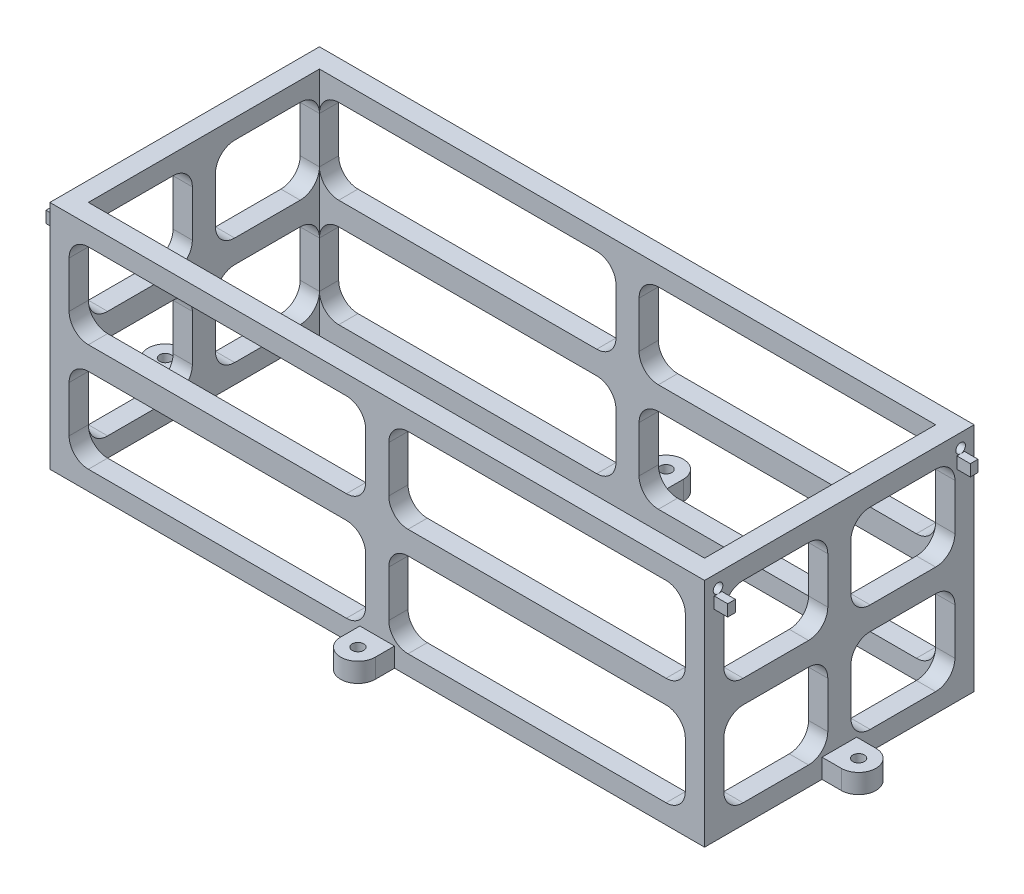
SolidWorks part; units mm, degrees
ref_plane "Front Plane" through (0, 0, 0) normal (0, 0, 1) x (1, 0, 0)
ref_plane "Top Plane" through (0, 0, 0) normal (0, 1, 0) x (1, 0, 0)
ref_plane "Right Plane" through (0, 0, 0) normal (1, 0, 0) x (0, 0, -1)
sketch "Sketch1" plane through (0, 0, 0) normal (0, 1, 0) x (1, 0, 0)
  line L1 (-85, -35) -> (85, -35)
  line L2 (-85, -35) -> (-85, 35)
  line L3 (-85, 35) -> (85, 35)
  line L4 (85, -35) -> (85, 35)
  line L5 (-85, -35) -> (85, 35) construction
  line L6 (-85, 35) -> (85, -35) construction
  point P0 (0, 0)
  dimension "D1" = 70
  dimension "D2" = 170
extrude "Boss-Extrude1" add sketch "Sketch1" along normal blind 60
shell "Shell1" thickness 5 removed face at (0, 60, 0) removed face at (0, 0, 0)
sketch "Sketch3" plane through (-85, 0, 0) normal (-1, 0, 0) x (0, 0, 1)
  line L0 (-35, 30) -> (35, 30) construction
  line L1 (-35, 60) -> (-35, 0) construction
  line L2 (35, 60) -> (35, 0) construction
  line L3 (-35, 60) -> (35, 60) construction
  line L4 (-30, 5) -> (30, 5)
  line L5 (-30, 5) -> (-30, 55)
  line L6 (-30, 55) -> (30, 55)
  line L7 (30, 5) -> (30, 55)
  line L8 (-30, 5) -> (30, 55) construction
  line L9 (-30, 55) -> (30, 5) construction
  point P6 (0, 30)
  dimension "D1" = 5
  dimension "D2" = 5
sketch "Sketch4" plane through (85, 0, 0) normal (1, 0, 0) x (0, 0, -1)
  line L0 (0, 60) -> (0, 0) construction
  line L1 (-35, 60) -> (35, 60) construction
  line L2 (-35, 30) -> (35, 30) construction
  line L3 (-35, 60) -> (-35, 0) construction
  line L4 (35, 60) -> (35, 0) construction
  line L5 (-35, 0) -> (35, 0) construction
  line L6 (-25, 55) -> (-8, 55)
  line L7 (-30, 50) -> (-30, 38)
  line L8 (-25, 33) -> (-8, 33)
  line L9 (-3, 50) -> (-3, 38)
  line L10 (-25, 27) -> (-8, 27)
  line L11 (-30, 22) -> (-30, 10)
  line L12 (-25, 5) -> (-8, 5)
  line L13 (-3, 22) -> (-3, 10)
  line L14 (8, 55) -> (25, 55)
  line L15 (3, 50) -> (3, 38)
  line L16 (8, 33) -> (25, 33)
  line L17 (30, 50) -> (30, 38)
  line L18 (8, 27) -> (25, 27)
  line L19 (3, 22) -> (3, 10)
  line L20 (8, 5) -> (25, 5)
  line L21 (30, 22) -> (30, 10)
  arc A0 (3, 38) -> (8, 33) centre (8, 38) ccw
  arc A1 (8, 27) -> (3, 22) centre (8, 22) ccw
  arc A2 (25, 5) -> (30, 10) centre (25, 10) ccw
  arc A3 (25, 27) -> (30, 22) centre (25, 22) cw
  arc A4 (25, 33) -> (30, 38) centre (25, 38) ccw
  arc A5 (25, 55) -> (30, 50) centre (25, 50) cw
  arc A6 (8, 55) -> (3, 50) centre (8, 50) ccw
  arc A7 (3, 10) -> (8, 5) centre (8, 10) ccw
  arc A8 (-8, 5) -> (-3, 10) centre (-8, 10) ccw
  arc A9 (-8, 27) -> (-3, 22) centre (-8, 22) cw
  arc A10 (-8, 33) -> (-3, 38) centre (-8, 38) ccw
  arc A11 (-8, 55) -> (-3, 50) centre (-8, 50) cw
  arc A12 (-30, 10) -> (-25, 5) centre (-25, 10) ccw
  arc A13 (-25, 27) -> (-30, 22) centre (-25, 22) ccw
  arc A14 (-30, 38) -> (-25, 33) centre (-25, 38) ccw
  arc A15 (-25, 55) -> (-30, 50) centre (-25, 50) ccw
  dimension "D17" = 5
  dimension "D1" = 5
  dimension "D2" = 5
  dimension "D3" = 5
  dimension "D4" = 5
  dimension "D5" = 5
  dimension "D6" = 5
  dimension "D7" = 5
  dimension "D8" = 5
  dimension "D9" = 3
  dimension "D10" = 3
  dimension "D11" = 3
  dimension "D12" = 3
  dimension "D13" = 3
  dimension "D14" = 3
  dimension "D15" = 3
  dimension "D16" = 3
extrude "Cut-Extrude1" cut sketch "Sketch4" against normal blind 170
sketch "Sketch5" plane through (0, 0, 35) normal (0, 0, 1) x (1, 0, 0)
  line L0 (0, 60) -> (0, 0) construction
  line L1 (-85, 60) -> (85, 60) construction
  line L2 (-85, 0) -> (85, 0) construction
  line L3 (-85, 30) -> (85, 30) construction
  line L4 (-85, 60) -> (-85, 0) construction
  line L5 (85, 60) -> (85, 0) construction
  line L7 (-75, 55) -> (-8, 55)
  line L8 (-80, 50) -> (-80, 38)
  line L9 (-75, 33) -> (-8, 33)
  line L10 (-3, 50) -> (-3, 38)
  line L11 (-75, 27) -> (-8, 27)
  line L12 (-80, 22) -> (-80, 10)
  line L13 (-75, 5) -> (-8, 5)
  line L14 (-3, 22) -> (-3, 10)
  line L15 (8, 55) -> (75, 55)
  line L16 (3, 50) -> (3, 38)
  line L17 (8, 33) -> (75, 33)
  line L18 (80, 50) -> (80, 38)
  line L19 (8, 27) -> (75, 27)
  line L20 (3, 22) -> (3, 10)
  line L21 (8, 5) -> (75, 5)
  line L22 (80, 22) -> (80, 10)
  arc A0 (75, 33) -> (80, 38) centre (75, 38) ccw
  arc A1 (75, 55) -> (80, 50) centre (75, 50) cw
  arc A2 (75, 5) -> (80, 10) centre (75, 10) ccw
  arc A3 (80, 22) -> (75, 27) centre (75, 22) ccw
  arc A4 (3, 10) -> (8, 5) centre (8, 10) ccw
  arc A5 (8, 27) -> (3, 22) centre (8, 22) ccw
  arc A6 (3, 38) -> (8, 33) centre (8, 38) ccw
  arc A7 (8, 55) -> (3, 50) centre (8, 50) ccw
  arc A8 (-8, 27) -> (-3, 22) centre (-8, 22) cw
  arc A9 (-8, 5) -> (-3, 10) centre (-8, 10) ccw
  arc A10 (-8, 55) -> (-3, 50) centre (-8, 50) cw
  arc A11 (-80, 10) -> (-75, 5) centre (-75, 10) ccw
  arc A12 (-75, 27) -> (-80, 22) centre (-75, 22) ccw
  arc A13 (-80, 38) -> (-75, 33) centre (-75, 38) ccw
  arc A14 (-75, 55) -> (-80, 50) centre (-75, 50) ccw
  arc A15 (-8, 33) -> (-3, 38) centre (-8, 38) ccw
  dimension "D17" = 5
  dimension "D18" = 5
  dimension "D1" = 5
  dimension "D2" = 5
  dimension "D3" = 5
  dimension "D4" = 5
  dimension "D5" = 5
  dimension "D6" = 5
  dimension "D7" = 5
  dimension "D8" = 5
  dimension "D9" = 3
  dimension "D10" = 3
  dimension "D11" = 3
  dimension "D12" = 3
  dimension "D13" = 3
  dimension "D14" = 3
  dimension "D15" = 3
  dimension "D16" = 3
extrude "Cut-Extrude2" cut sketch "Sketch5" against normal blind 90
sketch "Sketch6" plane through (0, 0, 0) normal (0, -1, 0) x (1, 0, 0)
  line L0 (0, 35) -> (0, -35) construction
  line L1 (-85, 35) -> (85, 35) construction
  line L2 (85, -35) -> (-85, -35) construction
  line L3 (-85, 0) -> (85, 0) construction
  line L4 (-85, -35) -> (-85, 35) construction
  line L5 (85, 35) -> (85, -35) construction
  line L6 (-80, 30) -> (80, 30) construction
  line L7 (4.5, 40) -> (-4.5, 40)
  line L8 (4.5, 40) -> (4.5, 30)
  line L9 (4.5, 30) -> (-4.5, 30)
  line L10 (-4.5, 40) -> (-4.5, 30)
  line L11 (4.5, 40) -> (-4.5, 30) construction
  line L12 (4.5, 30) -> (-4.5, 40) construction
  line L13 (-80, -30) -> (-80, 30) construction
  line L14 (-90, -4.5) -> (-80, -4.5)
  line L15 (-90, -4.5) -> (-90, 4.5)
  line L16 (-90, 4.5) -> (-80, 4.5)
  line L17 (-80, -4.5) -> (-80, 4.5)
  line L18 (-90, -4.5) -> (-80, 4.5) construction
  line L19 (-90, 4.5) -> (-80, -4.5) construction
  line L20 (80, -30) -> (-80, -30) construction
  line L21 (-4.5, -40) -> (4.5, -40)
  line L22 (-4.5, -40) -> (-4.5, -30)
  line L23 (-4.5, -30) -> (4.5, -30)
  line L24 (4.5, -40) -> (4.5, -30)
  line L25 (-4.5, -40) -> (4.5, -30) construction
  line L26 (-4.5, -30) -> (4.5, -40) construction
  line L27 (80, 30) -> (80, -30) construction
  line L28 (90, 4.5) -> (80, 4.5)
  line L29 (90, 4.5) -> (90, -4.5)
  line L30 (90, -4.5) -> (80, -4.5)
  line L31 (80, 4.5) -> (80, -4.5)
  line L32 (90, 4.5) -> (80, -4.5) construction
  line L33 (90, -4.5) -> (80, 4.5) construction
  circle A0 centre (0, 40) radius 4.5
  circle A1 centre (90, 0) radius 4.5
  circle A2 centre (0, -40) radius 4.5
  circle A3 centre (-90, 0) radius 4.5
  circle A4 centre (0, 40) radius 1.5
  circle A5 centre (90, 0) radius 1.5
  circle A6 centre (0, -40) radius 1.5
  circle A7 centre (-90, 0) radius 1.5
  dimension "D5" = 3
  dimension "D6" = 3
  dimension "D7" = 3
  dimension "D8" = 3
  dimension "D1" = 9
  dimension "D2" = 9
  dimension "D3" = 9
  dimension "D4" = 9
extrude "Boss-Extrude2" add sketch "Sketch6" against normal blind 5 contours L15 L14 L17 L16 | A3 | L8 L7 L10 L9 | A0 | L29 L28 L31 L30 | A1 | L22 L21 L24 L23 | A2 | A7
sketch "Sketch7" plane through (0, 0, 0) normal (0, -1, 0) x (1, 0, 0)
  line L0 (-90, -1.5) -> (-90, 1.5) construction
  circle A0 centre (0, 40) radius 1.5
  circle A1 centre (-90, 0) radius 1.5
  circle A2 centre (0, -40) radius 1.5
  circle A3 centre (90, 0) radius 1.5
  dimension "D1" = 3
  dimension "D2" = 3
  dimension "D3" = 3
  dimension "D4" = 3
extrude "Cut-Extrude3" cut sketch "Sketch7" against normal blind 5
sketch "Sketch8" plane through (85, 0, 0) normal (1, 0, 0) x (0, 0, -1)
  line L0 (-35, 60) -> (35, 60) construction
  line L1 (-35, 60) -> (-35, 0) construction
  line L2 (35, 60) -> (35, 0) construction
  circle A0 centre (-31.5, 56.5) radius 1.25
  circle A1 centre (31.5, 56.5) radius 1.25
  dimension "D1" = 2.5
  dimension "D2" = 2.5
  dimension "D3" = 3.5
  dimension "D4" = 3.5
  dimension "D5" = 3.5
  dimension "D6" = 3.5
extrude "Cut-Extrude4" cut sketch "Sketch8" against normal blind 5
sketch "Sketch9" plane through (-85, 0, 0) normal (-1, 0, 0) x (0, 0, 1)
  line L0 (-35, 60) -> (35, 60) construction
  line L1 (-35, 60) -> (-35, 0) construction
  line L2 (35, 60) -> (35, 0) construction
  circle A0 centre (-31.5, 56.5) radius 1.25
  circle A1 centre (31.5, 56.5) radius 1.25
  dimension "D1" = 2.5
  dimension "D2" = 2.5
  dimension "D3" = 3.5
  dimension "D4" = 3.5
  dimension "D5" = 3.5
  dimension "D6" = 3.5
extrude "Cut-Extrude5" cut sketch "Sketch9" against normal blind 5
sketch "Sketch10" plane through (-85, 0, 0) normal (-1, 0, 0) x (0, 0, 1)
  line L0 (-31.5, 56.5) -> (-31.5, 27.4167) construction
  line L1 (31.5, 56.5) -> (31.5, 27.8335) construction
  line L3 (-32.5, 52.25) -> (-30.5, 52.25)
  line L4 (-32.5, 52.25) -> (-32.5, 55.25)
  line L5 (-32.5, 55.25) -> (-30.5, 55.25)
  line L6 (-30.5, 52.25) -> (-30.5, 55.25)
  line L7 (-32.5, 52.25) -> (-30.5, 55.25) construction
  line L8 (-32.5, 55.25) -> (-30.5, 52.25) construction
  line L9 (30.5, 52.25) -> (32.5, 52.25)
  line L10 (30.5, 52.25) -> (30.5, 55.25)
  line L11 (30.5, 55.25) -> (32.5, 55.25)
  line L12 (32.5, 52.25) -> (32.5, 55.25)
  line L13 (30.5, 52.25) -> (32.5, 55.25) construction
  line L14 (30.5, 55.25) -> (32.5, 52.25) construction
  point P6 (-31.5, 53.75)
  point P11 (31.5, 53.75)
  dimension "D1" = 1.25
  dimension "D2" = 2
  dimension "D3" = 3
  dimension "D4" = 1.25
  dimension "D5" = 2
  dimension "D6" = 3
extrude "Boss-Extrude3" add sketch "Sketch10" along normal blind 3.5
sketch "Sketch11" plane through (85, 0, 0) normal (1, 0, 0) x (0, 0, -1)
  line L0 (-31.5, 56.5) -> (-31.5, 31.0757) construction
  line L1 (31.5, 56.5) -> (31.5, 30.4027) construction
  line L3 (-32.5, 52.25) -> (-30.5, 52.25)
  line L4 (-32.5, 52.25) -> (-32.5, 55.25)
  line L5 (-32.5, 55.25) -> (-30.5, 55.25)
  line L6 (-30.5, 52.25) -> (-30.5, 55.25)
  line L7 (-32.5, 52.25) -> (-30.5, 55.25) construction
  line L8 (-32.5, 55.25) -> (-30.5, 52.25) construction
  line L9 (30.5, 52.25) -> (32.5, 52.25)
  line L10 (30.5, 52.25) -> (30.5, 55.25)
  line L11 (30.5, 55.25) -> (32.5, 55.25)
  line L12 (32.5, 52.25) -> (32.5, 55.25)
  line L13 (30.5, 52.25) -> (32.5, 55.25) construction
  line L14 (30.5, 55.25) -> (32.5, 52.25) construction
  point P6 (-31.5, 53.75)
  point P11 (31.5, 53.75)
  dimension "D1" = 1.25
  dimension "D2" = 1.25
  dimension "D3" = 2
  dimension "D4" = 2
  dimension "D5" = 3
  dimension "D6" = 3
extrude "Boss-Extrude4" add sketch "Sketch11" along normal blind 3.5
